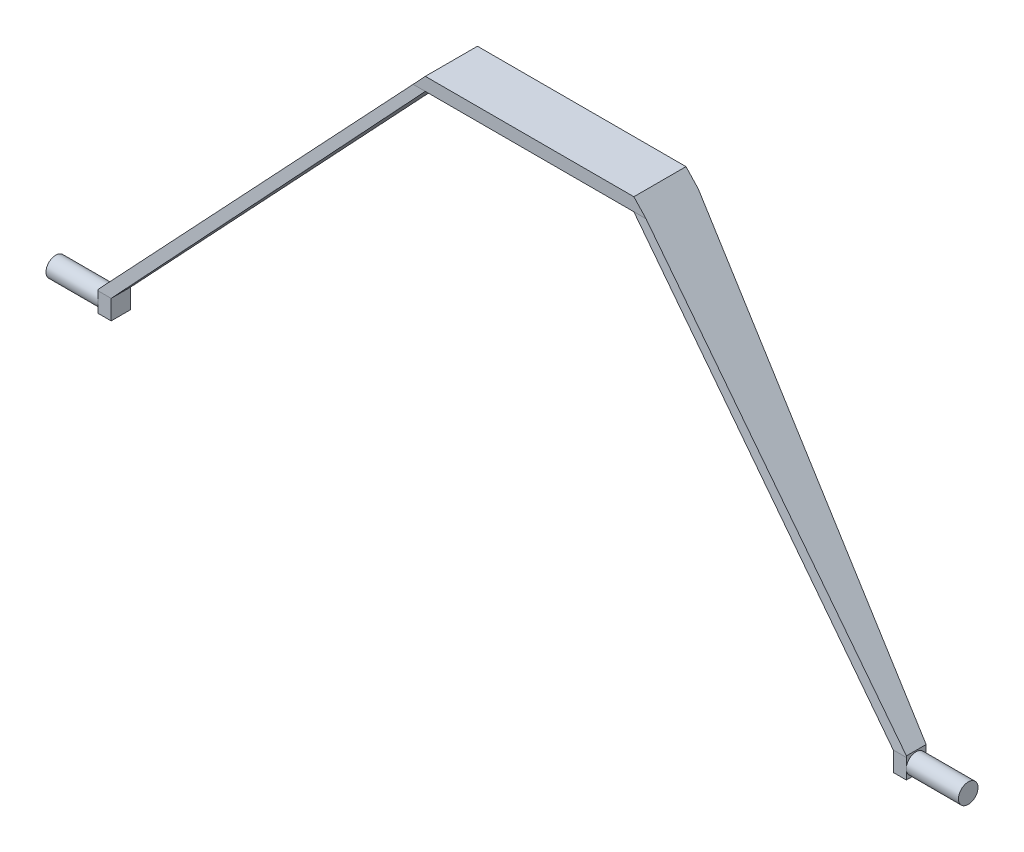
SolidWorks part; units mm, degrees
ref_plane "Front" through (0, 0, 0) normal (0, 0, 1) x (1, 0, 0)
ref_plane "Top" through (0, 0, 0) normal (0, 1, 0) x (1, 0, 0)
ref_plane "Right" through (0, 0, 0) normal (1, 0, 0) x (0, 0, -1)
sketch "Sketch12" plane through (0, 0, 0) normal (0, 0, 1) x (1, 0, 0)
  line L0 (-203.2, 241.3) -> (203.2, 241.3)
  line L1 (0, 241.3) -> (0, -425.45) construction
  line L2 (-203.2, 241.3) -> (-787.4717, -383.6692)
  line L3 (-787.4717, -383.6692) -> (-787.4717, -424.3092)
  line L4 (-787.4717, -424.3092) -> (-762.0717, -424.3092)
  line L5 (-762.0717, -424.3092) -> (-762.0717, -386.2092)
  line L6 (-762.0717, -386.2092) -> (-203.2, 215.9)
  line L7 (-203.2, 215.9) -> (203.2, 215.9)
  line L9 (762.0717, -386.2092) -> (203.2, 215.9)
  line L10 (762.0717, -424.3092) -> (762.0717, -386.2092)
  line L11 (787.4717, -424.3092) -> (762.0717, -424.3092)
  line L12 (787.4717, -383.6692) -> (787.4717, -424.3092)
  line L13 (203.2, 241.3) -> (787.4717, -383.6692)
  point P14 (0, 215.9)
  dimension "D1" = 666.75
  dimension "D2" = 40.64
  dimension "D3" = 25.4
  dimension "D4" = 38.1
extrude "Boss-Extrude6" add sketch "Sketch12" along normal blind 53.34 and the other way blind 101.6
sketch "Sketch13" plane through (787.4717, 0, 0) normal (1, 0, 0) x (0, 0, -1)
  line L0 (-53.34, -424.3092) -> (-53.34, -383.6692) construction
  line L1 (101.6, -424.3092) -> (-53.34, -424.3092) construction
  circle A0 centre (-34.29, -405.2592) radius 19.05
  dimension "D1" = 38.1
  dimension "D2" = 19.05
  dimension "D3" = 19.05
extrude "Boss-Extrude7" add sketch "Sketch13" along normal blind 101.6
mirror "Mirror1" about plane through (0, 0, 0) normal (1, 0, 0) of "Boss-Extrude7"
sketch "Sketch14" plane through (0, 0, 0) normal (1, 0, 0) x (0, 0, -1)
  line L0 (-53.34, 241.3) -> (0, 241.3) construction
  line L1 (101.6, 241.3) -> (-53.34, 241.3) construction
  line L2 (0, 241.3) -> (0, 215.9)
  line L5 (-53.34, -386.2092) -> (-15.24, -386.2092) construction
  line L6 (101.6, -386.2092) -> (-53.34, -386.2092) construction
  line L7 (0, 215.9) -> (-53.34, -386.2092)
  line L8 (-53.34, -386.2092) -> (-53.34, 241.3)
  line L9 (101.6, 215.9) -> (-15.24, -386.2092)
  line L10 (-15.24, -386.2092) -> (-15.24, -424.3092)
  line L11 (101.6, -424.3092) -> (-34.29, -424.3092) construction
  line L12 (-15.24, -424.3092) -> (101.6, -424.3092)
  line L13 (101.6, -424.3092) -> (101.6, 215.9)
  line L14 (-53.34, 241.3) -> (0, 241.3)
  dimension "D1" = 53.34
  dimension "D2" = 38.1
extrude "Cut-Extrude8" cut sketch "Sketch14" against normal up to surface and the other way up to surface up to face at (-495.3358, -71.1846, -24.13) other way up to face at (495.3358, -71.1846, -24.13)
